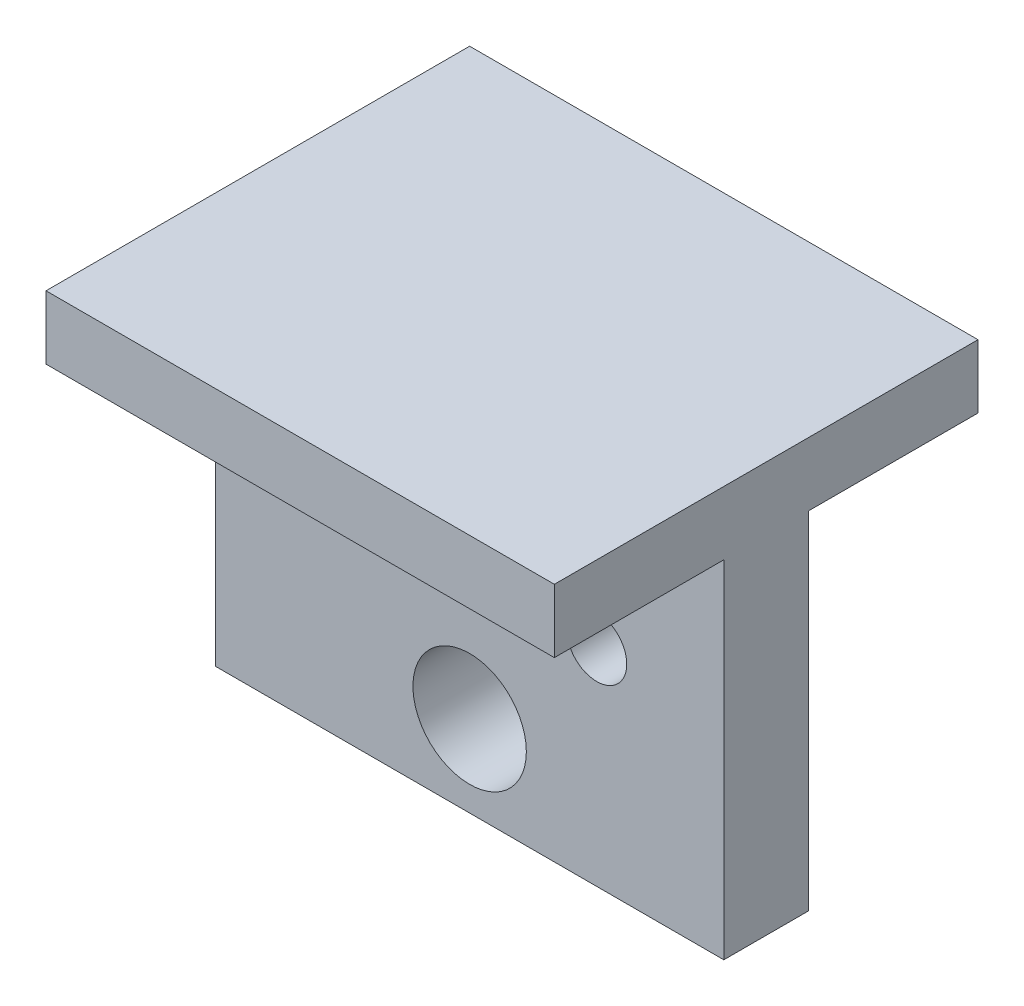
SolidWorks part; units mm, degrees
material "Acrylic (Medium-high impact)"
ref_plane "Front Plane" through (0, 0, 0) normal (0, 0, 1) x (1, 0, 0)
ref_plane "Top Plane" through (0, 0, 0) normal (0, 1, 0) x (1, 0, 0)
ref_plane "Right Plane" through (0, 0, 0) normal (1, 0, 0) x (0, 0, -1)
sketch "Sketch1" plane through (0, 0, 0) normal (0, 0, 1) x (1, 0, 0)
  line L2 (38.1, -12.224) -> (38.1, 12.224)
  line L4 (-38.1, -12.224) -> (-38.1, 12.224)
  line L8 (-38.1, -12.224) -> (38.1, -12.224)
  line L11 (-38.1, 39.7023) -> (-38.1, 12.224)
  line L12 (38.1, 12.224) -> (38.1, 39.7023)
  line L13 (-38.1, 39.7023) -> (-38.1, 49.2259)
  line L14 (-38.1, 39.7023) -> (38.1, 39.7023)
  line L16 (-38.1, 49.2259) -> (38.1, 49.2259)
  line L18 (38.1, 39.7023) -> (38.1, 49.2259)
  circle A0 centre (0, 0) radius 8.5
  circle A1 centre (19.05, 18.8743) radius 4.5
  circle A2 centre (-19.05, 18.8743) radius 4.5
  point P0 (0, 0)
  point P2 (0, 0)
  point P6 (-38.1, 0)
  dimension "D3" = 17
  dimension "D4" = 9
  dimension "D1" = 76.2
  dimension "D2" = 20.828
  dimension "D5" = 19.05
  dimension "D7" = 19.05
extrude "Boss-Extrude2" add sketch "Sketch1" along normal mid plane 63.5 contours L14 L18 L16 L13 region at (0, 44.4641, 0)
extrude "Boss-Extrude3" add sketch "Sketch1<6>" along normal mid plane 12.7 contours L14 L11 L4 L8 L2 L12 A2 A1 A0 region at (0, 14.4234, 0)
sketch "Sketch1<6>" plane through (0, 0, 0) normal (0, 0, 1) x (1, 0, 0) same geometry as "Sketch1"
